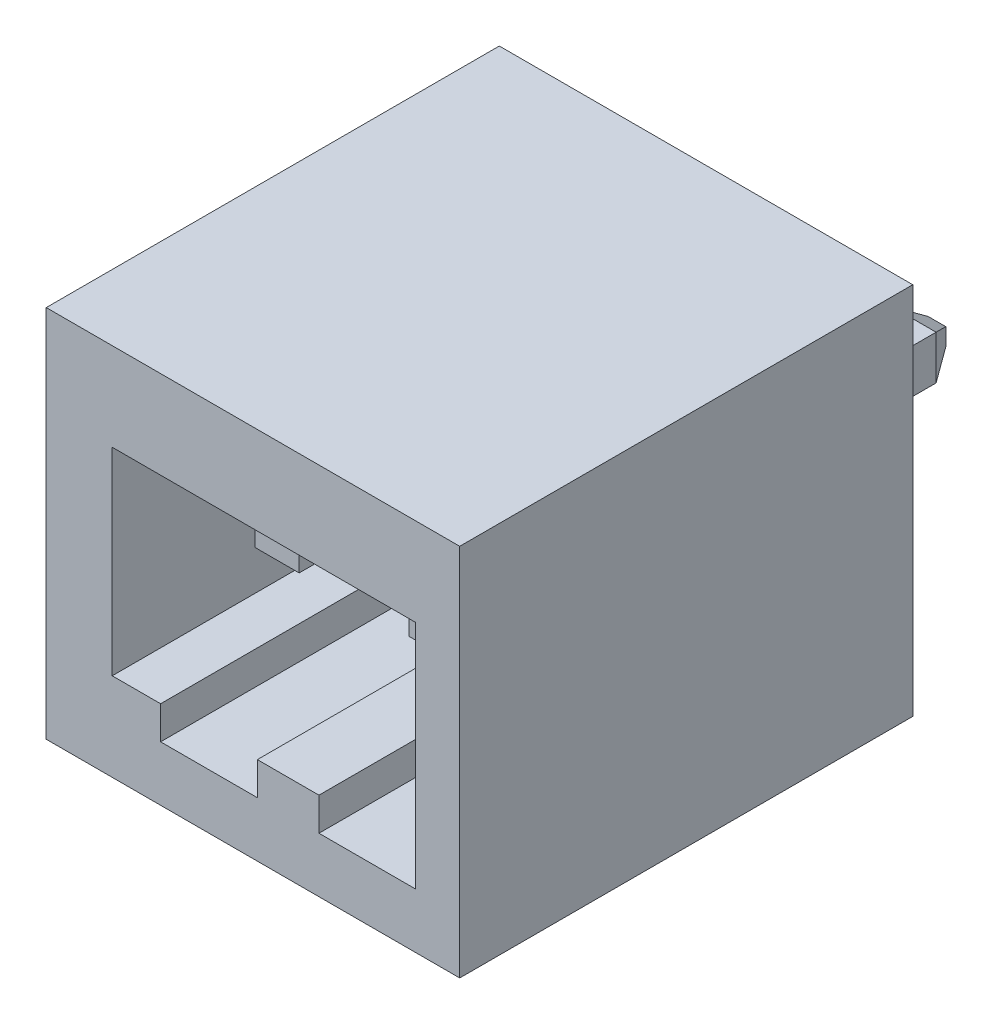
SolidWorks part; units mm, degrees
other "Детальный элемент1"
ref_plane "Спереди" through (0, 0, 0) normal (0, 0, 1) x (1, 0, 0)
ref_plane "Сверху" through (0, 0, 0) normal (0, 1, 0) x (1, 0, 0)
ref_plane "Справа" through (0, 0, 0) normal (1, 0, 0) x (0, 0, -1)
ref_axis "Ось1" through (80.9, 0, 0) along (-1, 0, 0)
sketch "Эскиз1" plane through (0, 0, 0) normal (0, 0, 1) x (1, 0, 0)
  line L0 (50, 0) -> (-50, 0) construction
  line L1 (-2.25, -0.5) -> (-1.25, -0.5)
  line L2 (-2.25, -0.5) -> (-2.25, 0.5)
  line L3 (-2.25, 0.5) -> (-1.25, 0.5)
  line L4 (-1.25, -0.5) -> (-1.25, 0.5)
  line L5 (-2.25, -0.5) -> (-1.25, 0.5) construction
  line L6 (-2.25, 0.5) -> (-1.25, -0.5) construction
  point P0 (-1.75, 0)
  dimension "D1" = 1.75
  dimension "D2" = 1
  dimension "D3" = 1
extrude "Бобышка-Вытянуть1" add sketch "Эскиз1" along normal blind 8 and the other way blind 3.5
chamfer "Фаска1" distance 0.3 angle 60 4 edges at (-1.75, -0.5, -3.5) (-2.25, 0, -3.5) (-1.75, 0.5, -3.5) (-1.25, 0, -3.5) first distance on face at (-1.75, 0, -3.5)
pattern_linear "Линейный массив1" count 2 spacing 3.5 along (1, 0, 0) of bodies 107
sketch "Эскиз3" plane through (0, 0, 0) normal (0, 0, 1) x (1, 0, 0)
  line L0 (0, -50) -> (0, 50) construction
  line L1 (4.7, 4.15) -> (-4.7, 4.15)
  line L2 (4.7, 4.15) -> (4.7, -4.35)
  line L3 (4.7, -4.35) -> (-4.7, -4.35)
  line L4 (-4.7, 4.15) -> (-4.7, -4.35)
  line L5 (4.7, 4.15) -> (-4.7, -4.35) construction
  line L6 (4.7, -4.35) -> (-4.7, 4.15) construction
  point P0 (0, -0.1)
  dimension "D1" = 8.5
  dimension "D2" = 9.4
  dimension "D3" = 4.35
extrude "Бобышка-Вытянуть2" add sketch "Эскиз3" along normal blind 10.3 separate body
shell "Оболочка1" thickness 2 removed face at (0, -0.1, 10.3)
sketch "Эскиз4" plane through (0, 0, 10.3) normal (0, 0, 1) x (1, 0, 0)
  line L0 (-3.2, -2.35) -> (3.7, -2.35) construction
  line L1 (-2.1, -2.35) -> (0.1, -2.35)
  line L2 (-2.1, -2.35) -> (-2.1, -3.1)
  line L3 (-2.1, -3.1) -> (0.1, -3.1)
  line L4 (0.1, -2.35) -> (0.1, -3.1)
  line L5 (-4.7, 4.15) -> (-4.7, -4.35) construction
  line L6 (1.5, -2.35) -> (3.7, -2.35)
  line L7 (1.5, -2.35) -> (1.5, -3.1)
  line L8 (1.5, -3.1) -> (3.7, -3.1)
  line L9 (3.7, -2.35) -> (3.7, -3.1)
  line L10 (4.7, -4.35) -> (4.7, 4.15) construction
  dimension "D1" = 2.2
  dimension "D2" = 0.75
  dimension "D3" = 4.8
  dimension "D4" = 3.2
extrude "Вырез-Вытянуть1" cut sketch "Эскиз4" against normal up to surface (8.8 mm away) up to face at (0.25, -0.1, 1.5)
